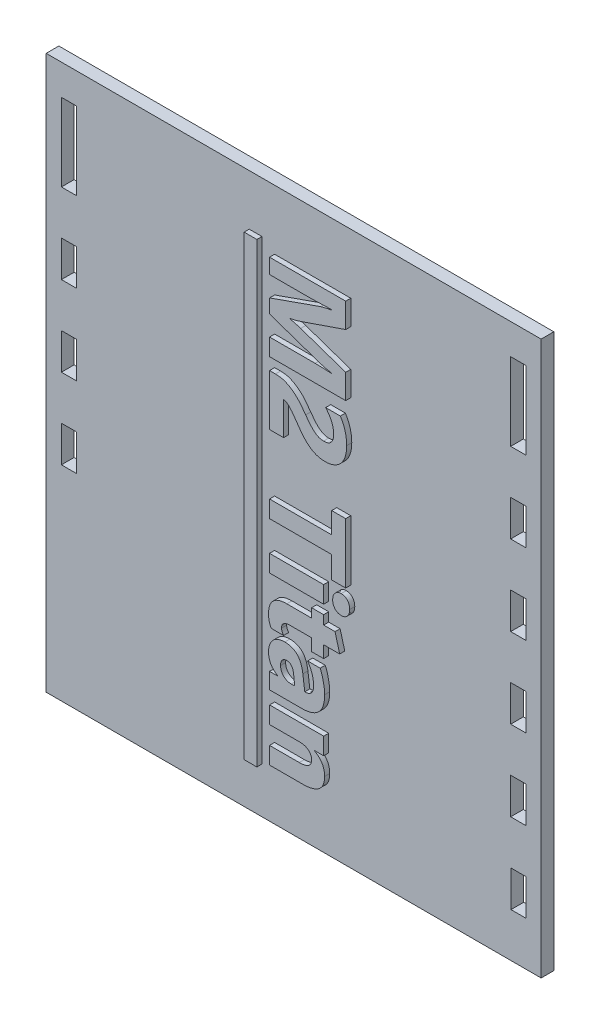
SolidWorks part; units mm, degrees
ref_plane "Front Plane" through (0, 0, 0) normal (0, 0, 1) x (1, 0, 0)
ref_plane "Top Plane" through (0, 0, 0) normal (0, 1, 0) x (1, 0, 0)
ref_plane "Right Plane" through (0, 0, 0) normal (1, 0, 0) x (0, 0, -1)
sketch "Sketch1" plane through (0, 0, 0) normal (0, 0, 1) x (1, 0, 0)
  line L1 (0, 0) -> (123.825, 0)
  line L2 (0, 0) -> (0, 138.43)
  line L3 (0, 138.43) -> (123.825, 138.43)
  line L4 (123.825, 0) -> (123.825, 138.43)
  dimension "D1" = 138.43
  dimension "D2" = 123.825
extrude "Boss-Extrude1" add sketch "Sketch1" along normal blind 3.175
sketch "Sketch2" plane through (0, 0, 3.175) normal (0, 0, 1) x (1, 0, 0)
  line L0 (3.81, 130.81) -> (120.015, 130.81) construction
  line L1 (3.81, 130.81) -> (3.81, 0) construction
  line L2 (0, 0) -> (123.825, 0) construction
  line L3 (3.81, 0) -> (120.015, 0) construction
  line L4 (120.015, 0) -> (120.015, 130.81) construction
  line L6 (0, 138.43) -> (0, 0) construction
  line L7 (123.825, 138.43) -> (0, 138.43) construction
  line L8 (7.62, -8.4363) -> (7.62, -12.2463) construction
  line L9 (3.81, 130.81) -> (7.62, 130.81)
  line L10 (3.81, 130.81) -> (3.81, 111.379)
  line L11 (3.81, 111.379) -> (7.62, 111.379)
  line L12 (7.62, 130.81) -> (7.62, 111.379)
  line L13 (3.81, 100.33) -> (7.62, 100.33)
  line L14 (3.81, 100.33) -> (3.81, 91.313)
  line L15 (3.81, 91.313) -> (7.62, 91.313)
  line L16 (7.62, 100.33) -> (7.62, 91.313)
  line L17 (3.81, 80.264) -> (7.62, 80.264)
  line L18 (3.81, 80.264) -> (3.81, 71.247)
  line L19 (3.81, 71.247) -> (7.62, 71.247)
  line L20 (7.62, 80.264) -> (7.62, 71.247)
  line L21 (3.81, 60.198) -> (7.62, 60.198)
  line L22 (3.81, 60.198) -> (3.81, 51.181)
  line L23 (3.81, 51.181) -> (7.62, 51.181)
  line L24 (7.62, 60.198) -> (7.62, 51.181)
  line L25 (116.205, 131.4965) -> (116.205, -11.8596) construction
  line L26 (120.015, 130.81) -> (116.205, 130.81)
  line L27 (120.015, 130.81) -> (120.015, 111.379)
  line L28 (120.015, 111.379) -> (116.205, 111.379)
  line L29 (116.205, 130.81) -> (116.205, 111.379)
  line L30 (120.015, 100.33) -> (116.205, 100.33)
  line L31 (120.015, 100.33) -> (120.015, 91.313)
  line L32 (120.015, 91.313) -> (116.205, 91.313)
  line L33 (116.205, 100.33) -> (116.205, 91.313)
  line L34 (120.015, 80.264) -> (116.205, 80.264)
  line L35 (120.015, 80.264) -> (120.015, 71.247)
  line L36 (120.015, 71.247) -> (116.205, 71.247)
  line L37 (116.205, 80.264) -> (116.205, 71.247)
  line L38 (120.015, 60.198) -> (116.205, 60.198)
  line L39 (120.015, 60.198) -> (120.015, 51.181)
  line L40 (120.015, 51.181) -> (116.205, 51.181)
  line L41 (116.205, 60.198) -> (116.205, 51.181)
  line L42 (120.015, 40.132) -> (116.205, 40.132)
  line L43 (120.015, 40.132) -> (120.015, 31.115)
  line L44 (120.015, 31.115) -> (116.205, 31.115)
  line L45 (116.205, 40.132) -> (116.205, 31.115)
  line L46 (120.015, 20.066) -> (116.2883, 20.066)
  line L47 (120.015, 20.066) -> (120.015, 11.049)
  line L48 (120.015, 11.049) -> (116.2883, 11.049)
  line L49 (116.2883, 20.066) -> (116.2883, 11.049)
  dimension "D1" = 116.205
  dimension "D2" = 3.81
  dimension "D3" = 7.62
  dimension "D4" = 19.431
  dimension "D5" = 9.017
  dimension "D6" = 3.81
  dimension "D7" = 3.81
  dimension "D8" = 3.81
  dimension "D9" = 19.431
  dimension "D10" = 11.049
  dimension "D11" = 11.049
  dimension "D12" = 11.049
  dimension "D13" = 11.049
  dimension "D14" = 11.049
  dimension "D15" = 11.049
  dimension "D16" = 11.049
  dimension "D17" = 11.049
extrude "Cut-Extrude1" cut sketch "Sketch2" against normal blind 3.81
sketch "Sketch5" plane through (0, 0, 3.175) normal (0, 0, 1) x (1, 0, 0)
  line L0 (57.15, 125.73) -> (57.15, 7.4832) construction
  line L1 (0, 138.43) -> (0, 0) construction
  line L2 (123.825, 138.43) -> (0, 138.43) construction
  line L4 (53.975, 125.73) -> (50.8, 125.73)
  line L5 (53.975, 125.73) -> (53.975, 11.43)
  line L6 (53.975, 11.43) -> (50.8, 11.43)
  line L7 (50.8, 125.73) -> (50.8, 11.43)
  text T0 "M2 Titan" font "Gadugi" height 19.05
  point P3 (57.15, 7.4832)
  dimension "D1" = 57.15
  dimension "D2" = 12.7
  dimension "D3" = 114.3
  dimension "D4" = 3.175
  dimension "D5" = 12.7
  dimension "D6" = 50.8
extrude "Boss-Extrude2" add sketch "Sketch5" along normal blind 1.27
